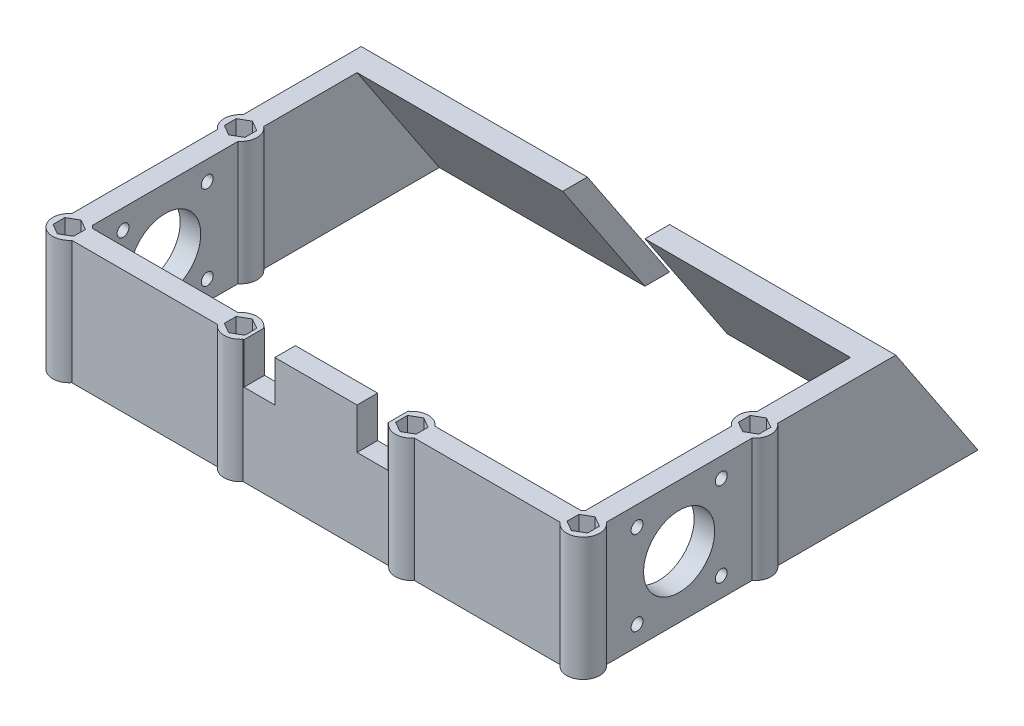
SolidWorks part; units mm, degrees
material "TPU"
ref_plane "Front Plane" through (0, 0, 0) normal (0, 0, 1) x (1, 0, 0)
ref_plane "Top Plane" through (0, 0, 0) normal (0, 1, 0) x (1, 0, 0)
ref_plane "Right Plane" through (0, 0, 0) normal (1, 0, 0) x (0, 0, -1)
sketch "Sketch4" plane through (0, 0, 0) normal (0, 1, 0) x (1, 0, 0)
  line L0 (0, 0) -> (0, -54.2428)
  line L1 (0, -114.3) -> (52.1261, -114.3) construction
  line L2 (165.1, -107.1594) -> (165.1, -62.1739)
  line L3 (165.1, 0) -> (158.75, 0)
  line L4 (158.75, 0) -> (158.75, -54.2428)
  line L7 (6.35, 0) -> (0, 0)
  line L8 (3.175, -111.125) -> (56.0917, -111.125) construction
  line L9 (56.0917, -111.125) -> (109.0083, -111.125) construction
  line L10 (109.0083, -111.125) -> (161.925, -111.125) construction
  line L11 (161.925, -111.125) -> (161.925, -58.2083) construction
  line L12 (6.35, -107.1594) -> (6.35, -62.1739)
  line L13 (6.35, -54.2428) -> (6.35, 0)
  line L14 (0, -62.1739) -> (0, -114.3) construction
  line L15 (0, -62.1739) -> (0, -107.1594)
  line L16 (7.1406, -114.3) -> (52.1261, -114.3)
  line L17 (52.1261, -107.95) -> (7.1406, -107.95)
  line L18 (60.0572, -114.3) -> (105.0428, -114.3) construction
  line L19 (60.0572, -114.3) -> (105.0428, -114.3)
  line L20 (105.0428, -107.95) -> (60.0572, -107.95)
  line L21 (112.9739, -114.3) -> (165.1, -114.3) construction
  line L22 (112.9739, -114.3) -> (157.9594, -114.3)
  line L23 (158.75, -62.1739) -> (158.75, -107.1594)
  line L24 (165.1, -54.2428) -> (165.1, 0)
  line L26 (157.9594, -107.95) -> (112.9739, -107.95)
  line L27 (0, -56.3752) -> (0, -60.0414)
  line L28 (0, -60.0414) -> (3.175, -61.8745)
  line L29 (3.175, -61.8745) -> (6.35, -60.0414)
  line L30 (6.35, -60.0414) -> (6.35, -56.3752)
  line L31 (6.35, -56.3752) -> (3.175, -54.5422)
  line L32 (3.175, -54.5422) -> (0, -56.3752)
  line L33 (3.175, -107.4588) -> (0, -109.2919)
  line L34 (0, -109.2919) -> (0, -112.9581)
  line L35 (0, -112.9581) -> (3.175, -114.7912)
  line L36 (3.175, -114.7912) -> (6.35, -112.9581)
  line L37 (6.35, -112.9581) -> (6.35, -109.2919)
  line L38 (6.35, -109.2919) -> (3.175, -107.4588)
  line L39 (56.0917, -107.4588) -> (52.9167, -109.2919)
  line L40 (52.9167, -109.2919) -> (52.9167, -112.9581)
  line L41 (52.9167, -112.9581) -> (56.0917, -114.7912)
  line L42 (56.0917, -114.7912) -> (59.2667, -112.9581)
  line L43 (59.2667, -112.9581) -> (59.2667, -109.2919)
  line L44 (59.2667, -109.2919) -> (56.0917, -107.4588)
  line L45 (109.0083, -107.4588) -> (105.8333, -109.2919)
  line L46 (105.8333, -109.2919) -> (105.8333, -112.9581)
  line L47 (105.8333, -112.9581) -> (109.0083, -114.7912)
  line L48 (109.0083, -114.7912) -> (112.1833, -112.9581)
  line L49 (112.1833, -112.9581) -> (112.1833, -109.2919)
  line L50 (112.1833, -109.2919) -> (109.0083, -107.4588)
  line L51 (161.925, -107.4588) -> (158.75, -109.2919)
  line L52 (158.75, -109.2919) -> (158.75, -112.9581)
  line L53 (158.75, -112.9581) -> (161.925, -114.7912)
  line L54 (161.925, -114.7912) -> (165.1, -112.9581)
  line L55 (165.1, -112.9581) -> (165.1, -109.2919)
  line L56 (165.1, -109.2919) -> (161.925, -107.4588)
  line L57 (161.925, -54.5422) -> (158.75, -56.3752)
  line L58 (158.75, -56.3752) -> (158.75, -60.0414)
  line L59 (158.75, -60.0414) -> (161.925, -61.8745)
  line L60 (161.925, -61.8745) -> (165.1, -60.0414)
  line L61 (165.1, -60.0414) -> (165.1, -56.3752)
  line L62 (165.1, -56.3752) -> (161.925, -54.5422)
  arc A6 (0, -54.2428) -> (0, -62.1739) centre (3.175, -58.2083) ccw
  arc A7 (6.35, -62.1739) -> (6.35, -54.2428) centre (3.175, -58.2083) ccw
  arc A8 (0, -107.1594) -> (7.1406, -114.3) centre (3.175, -111.125) ccw
  arc A9 (60.0572, -107.95) -> (52.1261, -107.95) centre (56.0917, -111.125) ccw
  arc A10 (52.1261, -114.3) -> (60.0572, -114.3) centre (56.0917, -111.125) ccw
  arc A11 (105.0428, -114.3) -> (112.9739, -114.3) centre (109.0083, -111.125) ccw
  arc A12 (112.9739, -107.95) -> (105.0428, -107.95) centre (109.0083, -111.125) ccw
  arc A13 (157.9594, -114.3) -> (165.1, -107.1594) centre (161.925, -111.125) ccw
  arc A14 (158.75, -54.2428) -> (158.75, -62.1739) centre (161.925, -58.2083) ccw
  arc A15 (165.1, -62.1739) -> (165.1, -54.2428) centre (161.925, -58.2083) ccw
  arc A16 (6.35, -107.1594) -> (7.1406, -107.95) centre (3.175, -111.125) cw
  arc A17 (158.75, -107.1594) -> (157.9594, -107.95) centre (161.925, -111.125) ccw
  circle A18 centre (3.175, -58.2083) radius 3.175 construction
  circle A19 centre (3.175, -111.125) radius 3.175 construction
  circle A20 centre (56.0917, -111.125) radius 3.175 construction
  circle A21 centre (109.0083, -111.125) radius 3.175 construction
  circle A22 centre (161.925, -111.125) radius 3.175 construction
  circle A23 centre (161.925, -58.2083) radius 3.175 construction
  point P30 (161.925, 0)
  point P51 (3.175, 0)
  dimension "D6" = 6.35
  dimension "D8" = 5.08
  dimension "D10" = 10.16
  dimension "D11" = 5.08
  dimension "D12" = 5.08
  dimension "D13" = 10.16
  dimension "D14" = 10.16
  dimension "D15" = 6.35
  dimension "D16" = 6.35
  dimension "D17" = 6.35
  dimension "D18" = 6.35
  dimension "D19" = 6.35
  dimension "D2" = 6.35
  dimension "D3" = 6.35
  dimension "D4" = 165.1
  dimension "D5" = 114.3
  dimension "D7" = 3.175
  dimension "D9" = 6.35
extrude "Boss-Extrude2" add sketch "Sketch4" along normal blind 38.1
chamfer "Chamfer2" distance 38.1 distance2 25.4 2 edges at (161.925, 38.1, 0) (3.175, 38.1, 0) first distance on face at (161.925, 19.05, 0) first distance on face at (3.175, 19.05, 0)
sketch "Sketch6" plane through (0, 0, 114.3) normal (0, 0, 1) x (1, 0, 0)
  line L0 (60.325, 38.1) -> (60.325, 25.4)
  line L1 (60.0572, 38.1) -> (105.0428, 38.1) construction
  line L2 (60.325, 25.4) -> (69.85, 25.4)
  line L3 (69.85, 25.4) -> (69.85, 38.1)
  line L4 (95.25, 38.1) -> (95.25, 25.4)
  line L5 (95.25, 25.4) -> (104.775, 25.4)
  line L6 (104.775, 25.4) -> (104.775, 38.1)
  line L7 (95.25, 38.1) -> (104.775, 38.1)
  line L8 (60.325, 38.1) -> (69.85, 38.1)
  line L9 (60.0572, 38.1) -> (60.325, 38.1) construction
  line L10 (104.775, 38.1) -> (105.0428, 38.1) construction
  dimension "D1" = 9.525
  dimension "D2" = 9.525
  dimension "D3" = 12.7
  dimension "D4" = 12.7
  dimension "D5" = 25.4
extrude "Cut-Extrude3" cut sketch "Sketch6" against normal through all
sketch "Sketch7" plane through (165.1, 0, 0) normal (1, 0, 0) x (0, 0, -1)
  line L0 (-71.6667, 32.05) -> (-97.6667, 6.05) construction
  line L1 (-71.6667, 32.05) -> (-71.6667, 6.05) construction
  line L2 (-71.6667, 6.05) -> (-97.6667, 6.05) construction
  line L3 (-97.6667, 6.05) -> (-97.6667, 32.05) construction
  line L4 (-97.6667, 32.05) -> (-71.6667, 32.05) construction
  line L6 (-116.205, 38.1) -> (-116.205, 0) construction
  line L7 (-116.205, 19.05) -> (-84.6667, 19.05) construction
  line L8 (-84.6667, 19.05) -> (-84.6667, 38.1) construction
  line L9 (-107.1594, 38.1) -> (-62.1739, 38.1) construction
  circle A0 centre (-84.6667, 19.05) radius 10.9855
  circle A1 centre (-71.6667, 32.05) radius 1.8415
  circle A2 centre (-71.6667, 6.05) radius 1.8415
  circle A3 centre (-97.6667, 6.05) radius 1.8415
  circle A4 centre (-97.6667, 32.05) radius 1.8415
  dimension "D2" = 21.971
  dimension "D3" = 3.683
  dimension "D1" = 26
extrude "Cut-Extrude4" cut sketch "Sketch7" against normal through all
sketch "Sketch8" plane through (0, 0, 0) normal (0, 0.5547, -0.8321) x (-1, 0, 0)
  line L0 (-165.1, 45.7905) -> (-95.25, 45.7905)
  line L1 (-95.25, 45.7905) -> (-95.25, 0)
  line L2 (-95.25, 0) -> (-165.1, 0)
  line L3 (-165.1, 0) -> (-165.1, 45.7905)
  line L4 (-69.85, 45.7905) -> (0, 45.7905)
  line L5 (0, 45.7905) -> (0, 0)
  line L6 (0, 0) -> (-69.85, 0)
  line L7 (-69.85, 0) -> (-69.85, 45.7905)
extrude "Boss-Extrude3" add sketch "Sketch8" along normal blind 6.35
sketch "Sketch9" plane through (165.1, 0, 0) normal (1, 0, 0) x (0, 0, -1)
  line L0 (-25.4, 38.1) -> (-17.7682, 38.1)
  line L1 (-20.1165, 41.6223) -> (5.2835, 3.5223) construction
  line L2 (-17.7682, 38.1) -> (-20.1165, 41.6223)
  line L3 (-20.1165, 41.6223) -> (-25.4, 38.1)
extrude "Cut-Extrude5" cut sketch "Sketch9" against normal through all and the other way through all
sketch "Sketch10" plane through (165.1, 0, 0) normal (1, 0, 0) x (0, 0, -1)
  line L0 (0, 0) -> (7.6318, 0)
  line L1 (7.6318, 0) -> (5.2835, 3.5223)
  line L2 (-17.7682, 38.1) -> (5.2835, 3.5223) construction
  line L3 (5.2835, 3.5223) -> (0, 0)
extrude "Boss-Extrude4" add sketch "Sketch10" against normal up to surface (69.85 mm away) up to face at (95.25, 19.9306, 9.4712)
sketch "Sketch11" plane through (0, 0, 0) normal (-1, 0, 0) x (0, 0, 1)
  line L0 (-5.2835, 3.5223) -> (-7.6318, 0)
  line L1 (-7.6318, 0) -> (0, 0)
  line L2 (0, 0) -> (-5.2835, 3.5223)
extrude "Boss-Extrude5" add sketch "Sketch11" against normal up to surface (69.85 mm away) up to face at (69.85, 19.9306, 9.4712)
